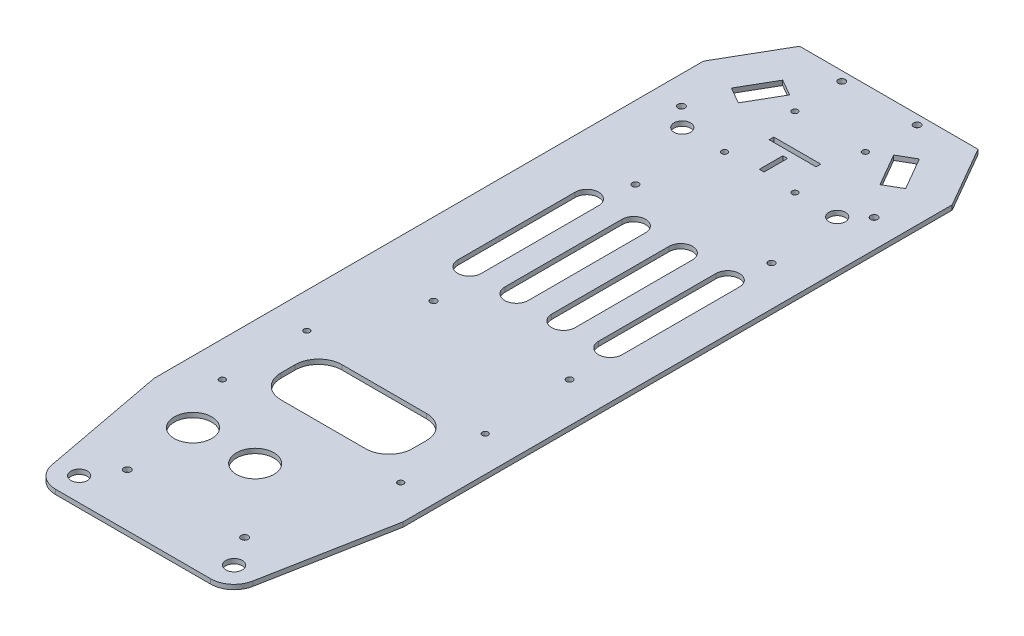
SolidWorks part; units mm, degrees
material "Epoxy, renforcé"
ref_plane "Plan de face" through (0, 0, 0) normal (0, 0, 1) x (1, 0, 0)
ref_plane "Plan de dessus" through (0, 0, 0) normal (0, 1, 0) x (1, 0, 0)
ref_plane "Plan de droite" through (0, 0, 0) normal (1, 0, 0) x (0, 0, -1)
sketch "Esquisse1" plane through (0, 0, 0) normal (0, 1, 0) x (1, 0, 0)
  line L0 (-33, 128.5) -> (33, 128.5) construction
  line L1 (33, 128.5) -> (33, -128.5) construction
  line L2 (33, -128.5) -> (-33, -128.5) construction
  line L3 (-33, -128.5) -> (-33, 128.5) construction
  line L4 (0, 128.5) -> (0, 0) construction
  line L5 (33, 0) -> (0, 0) construction
  line L6 (53, 183.5) -> (-53, 183.5)
  line L7 (-53, 183.5) -> (-53, -148.5)
  line L8 (-53, -148.5) -> (53, -148.5)
  line L9 (53, 183.5) -> (53, -148.5)
  circle A0 centre (-33, 128.5) radius 3.5
  circle A1 centre (-33, -128.5) radius 3.5
  circle A2 centre (33, 128.5) radius 3.5
  circle A3 centre (33, -128.5) radius 3.5
  point P17 (0, -148.5)
  point P18 (0, 183.5)
  dimension "D1" = 7
  dimension "D2" = 7
  dimension "D3" = 7
  dimension "D4" = 7
  dimension "D5" = 66
  dimension "D6" = 257
  dimension "D7" = 55
  dimension "D8" = 20
  dimension "D9" = 20
extrude "Boss.-Extru.1" add sketch "Esquisse1" along normal blind 2
sketch "Esquisse3" plane through (0, 2, 0) normal (0, 1, 0) x (1, 0, 0)
  line L0 (-22, 11.5) -> (-22, 97.5) construction
  line L1 (-22, 97.5) -> (36, 97.5) construction
  line L2 (36, 97.5) -> (36, 11.5) construction
  line L3 (36, 11.5) -> (-22, 11.5) construction
  line L4 (53, -148.5) -> (53, 183.5) construction
  line L5 (53, 183.5) -> (-53, 183.5) construction
  circle A4 centre (-22, 11.5) radius 1.375
  circle A5 centre (-22, 97.5) radius 1.375
  circle A6 centre (36, 97.5) radius 1.375
  circle A7 centre (36, 11.5) radius 1.375
  dimension "D1" = 86
  dimension "D2" = 58
  dimension "D3" = 17
  dimension "D4" = 86
extrude "Enlèv. mat.-Extru.1" cut sketch "Esquisse3" against normal through all
chamfer "Chanfrein1" distance 15 angle 60 2 edges at (-53, 1, -183.5) (53, 1, -183.5) first distance on face at (0, 1, -183.5)
sketch "Esquisse4" plane through (0, 2, 0) normal (0, 1, 0) x (1, 0, 0)
  line L0 (0, -62.5) -> (0, -148.5) construction
  line L1 (38, -62.5) -> (-38, -62.5) construction
  line L2 (38, -62.5) -> (38, -26.5) construction
  line L3 (38, -26.5) -> (-38, -26.5) construction
  line L4 (-38, -62.5) -> (-38, -26.5) construction
  line L5 (-53, -148.5) -> (53, -148.5) construction
  line L6 (38, 183.5) -> (-38, 183.5) construction
  line L7 (-28, -57.5) -> (28, -57.5)
  line L8 (-28, -57.5) -> (-28, -31.5)
  line L9 (-28, -31.5) -> (28, -31.5)
  line L10 (28, -57.5) -> (28, -31.5)
  circle A0 centre (38, -62.5) radius 1.25
  circle A1 centre (38, -26.5) radius 1.25
  circle A2 centre (-38, -62.5) radius 1.25
  circle A3 centre (-38, -26.5) radius 1.25
  dimension "D3" = 2.5
  dimension "D4" = 2.5
  dimension "D5" = 2.5
  dimension "D6" = 2.5
  dimension "D1" = 76
  dimension "D2" = 36
  dimension "D7" = 210
  dimension "D8" = 10
  dimension "D9" = 10
  dimension "D10" = 10
  dimension "D11" = 10
extrude "Enlèv. mat.-Extru.2" cut sketch "Esquisse4" against normal blind 10
fillet "Congé1" radius 10 4 edges at (28, 1, 57.5) (28, 1, 31.5) (-28, 1, 31.5) (-28, 1, 57.5)
sketch "Esquisse5" plane through (0, 2, 0) normal (0, 1, 0) x (1, 0, 0)
  line L1 (-22, 11.5) -> (36, 11.5) construction
  line L2 (-22, 11.5) -> (-22, 97.5) construction
  line L3 (-22, 97.5) -> (36, 97.5) construction
  line L4 (36, 11.5) -> (36, 97.5) construction
  line L5 (-17, 16.5) -> (23.5, 16.5)
  line L6 (-17, 16.5) -> (-17, 92.5)
  line L7 (-17, 92.5) -> (23.5, 92.5)
  line L8 (23.5, 16.5) -> (23.5, 92.5)
  dimension "D1" = 10
  dimension "D2" = 10
  dimension "D3" = 25
  dimension "D4" = 10
extrude "Enlèv. mat.-Extru.3" [suppressed] cut sketch "Esquisse5" against normal blind 10
fillet "Congé2" [suppressed] radius 10
sketch "Esquisse6" plane through (0, 2, 0) normal (0, 1, 0) x (1, 0, 0)
  line L0 (0, 183.5) -> (0, 143.5) construction
  line L2 (38, 183.5) -> (-38, 183.5) construction
  line L3 (15, 128.5) -> (-15, 128.5) construction
  line L4 (15, 128.5) -> (15, 158.5) construction
  line L5 (15, 158.5) -> (-15, 158.5) construction
  line L6 (-15, 128.5) -> (-15, 158.5) construction
  line L7 (15, 128.5) -> (-15, 158.5) construction
  line L8 (15, 158.5) -> (-15, 128.5) construction
  line L9 (-10, 142.5) -> (10, 142.5)
  line L10 (-10, 142.5) -> (-10, 144.5)
  line L11 (-10, 144.5) -> (10, 144.5)
  line L12 (10, 142.5) -> (10, 144.5)
  line L13 (-10, 142.5) -> (10, 144.5) construction
  line L14 (-10, 144.5) -> (10, 142.5) construction
  line L15 (-1.1799, 129.5) -> (0.8201, 129.5)
  line L16 (-1.1799, 129.5) -> (-1.1799, 139.5)
  line L17 (-1.1799, 139.5) -> (0.8201, 139.5)
  line L18 (0.8201, 129.5) -> (0.8201, 139.5)
  line L19 (-1.1799, 129.5) -> (0.8201, 139.5) construction
  line L20 (-1.1799, 139.5) -> (0.8201, 129.5) construction
  circle A0 centre (-15, 128.5) radius 1.25
  circle A1 centre (15, 128.5) radius 1.25
  circle A2 centre (-15, 158.5) radius 1.25
  circle A3 centre (15, 158.5) radius 1.25
  point P16 (-0.1799, 134.5)
  dimension "D4" = 2.5
  dimension "D5" = 2.5
  dimension "D6" = 2.5
  dimension "D7" = 2.5
  dimension "D1" = 30
  dimension "D2" = 30
  dimension "D3" = 40
  dimension "D8" = 20
  dimension "D9" = 2
  dimension "D10" = 10
  dimension "D11" = 2
  dimension "D12" = 3
extrude "Enlèv. mat.-Extru.4" cut sketch "Esquisse6" against normal blind 10
sketch "Esquisse7" plane through (0, 2, 0) normal (0, 1, 0) x (1, 0, 0)
  line L0 (0, -86.5) -> (0, -148.5) construction
  line L1 (-53, -148.5) -> (53, -148.5) construction
  line L2 (0, -86.5) -> (-53, -86.5) construction
  line L3 (-53, 157.5192) -> (-53, -148.5) construction
  line L4 (38, 183.5) -> (-38, 183.5) construction
  circle A0 centre (0, -86.5) radius 8
  circle A1 centre (-26.5, -86.5) radius 8
  dimension "D1" = 16
  dimension "D3" = 16
  dimension "D2" = 270
extrude "Enlèv. mat.-Extru.5" cut sketch "Esquisse7" against normal blind 10
sketch "Esquisse8" plane through (0, 2, 0) normal (0, 1, 0) x (1, 0, 0)
  line L0 (38, 183.5) -> (-38, 183.5)
  line L1 (38, 183.5) -> (-38, 183.5) construction
  line L2 (-38, 183.5) -> (-53, 157.5192)
  line L3 (-53, 157.5192) -> (-53, -76.5)
  line L4 (-53, 157.5192) -> (-53, -148.5) construction
  line L5 (-53, -76.5) -> (-42.8262, -130.3562)
  line L6 (-33, -138.5) -> (33, -138.5)
  line L7 (0, -148.5) -> (0, 183.5) construction
  line L8 (-53, -148.5) -> (53, -148.5) construction
  line L9 (53, -76.5) -> (42.8262, -130.3562)
  line L10 (53, 157.5192) -> (53, -76.5)
  line L11 (38, 183.5) -> (53, 157.5192)
  arc A0 (-42.8262, -130.3562) -> (-33, -138.5) centre (-33, -128.5) ccw
  arc A1 (42.8262, -130.3562) -> (33, -138.5) centre (33, -128.5) cw
  point P22 (0, -138.5)
  dimension "D1" = 20
  dimension "D2" = 260
extrude "Enlèv. mat.-Extru.6" cut sketch "Esquisse8" against normal blind 10 flip side to cut
sketch "Esquisse9" plane through (0, 2, 0) normal (0, 1, 0) x (1, 0, 0)
  line L0 (53, 10.4239) -> (-53, 10.4239) construction
  line L1 (53, -76.5) -> (53, 157.5192) construction
  line L2 (-53, 157.5192) -> (-53, -76.5) construction
  circle A0 centre (45, 10.4239) radius 3.5
  circle A1 centre (-45, 10.4239) radius 3.5
  dimension "D1" = 7
  dimension "D3" = 7
  dimension "D2" = 8
  dimension "D4" = 8
extrude "Enlèv. mat.-Extru.7" [suppressed] cut sketch "Esquisse9" against normal blind 10
sketch "Esquisse10" plane through (0, 0, 0) normal (0, -1, 0) x (1, 0, 0)
  line L0 (38, -183.5) -> (53, -157.5192) construction
  line L1 (55.5, -153.1891) -> (37.3135, -142.6891) construction
  line L2 (55.5, -153.1891) -> (38, -183.5) construction
  line L3 (38, -183.5) -> (19.8135, -173) construction
  line L4 (37.3135, -142.6891) -> (19.8135, -173) construction
  line L5 (55.5, -153.1891) -> (19.8135, -173) construction
  line L6 (38, -183.5) -> (37.3135, -142.6891) construction
  line L7 (28.5635, -157.8446) -> (37.6567, -163.0946) construction
  line L8 (32.5635, -150.9164) -> (30.1819, -149.5414)
  line L9 (30.1819, -149.5414) -> (26.1868, -156.461)
  line L10 (32.5635, -150.9164) -> (37.1101, -153.5414)
  line L11 (37.1101, -153.5414) -> (29.1101, -167.3978)
  line L12 (24.5635, -164.7728) -> (29.1101, -167.3978)
  line L13 (22.1819, -163.3978) -> (26.1868, -156.461)
  line L14 (24.5635, -164.7728) -> (22.1819, -163.3978)
  line L15 (0, -183.5) -> (0, -146.2698) construction
  line L16 (28.5635, -157.8446) -> (16.0635, -179.4952) construction
  line L18 (38, -183.5) -> (-38, -183.5) construction
  line L19 (-28.5635, -157.8446) -> (-37.6567, -163.0946) construction
  line L20 (-38, -183.5) -> (-37.3135, -142.6891) construction
  line L21 (-55.5, -153.1891) -> (-19.8135, -173) construction
  line L22 (-37.3135, -142.6891) -> (-19.8135, -173) construction
  line L23 (-38, -183.5) -> (-19.8135, -173) construction
  line L24 (-55.5, -153.1891) -> (-38, -183.5) construction
  line L25 (-55.5, -153.1891) -> (-37.3135, -142.6891) construction
  line L26 (-24.5635, -164.7728) -> (-22.1819, -163.3978)
  line L27 (-22.1819, -163.3978) -> (-26.1868, -156.461)
  line L28 (-24.5635, -164.7728) -> (-29.1101, -167.3978)
  line L29 (-37.1101, -153.5414) -> (-29.1101, -167.3978)
  line L30 (-32.5635, -150.9164) -> (-37.1101, -153.5414)
  line L31 (-30.1819, -149.5414) -> (-26.1868, -156.461)
  line L32 (-32.5635, -150.9164) -> (-30.1819, -149.5414)
  circle A0 centre (16.0635, -179.4952) radius 1.5
  circle A1 centre (41.0635, -136.1939) radius 1.5
  circle A2 centre (-41.0635, -136.1939) radius 1.5
  circle A3 centre (-16.0635, -179.4952) radius 1.5
  point P0 (37.6567, -163.0946)
  point P16 (33.1101, -160.4696)
  point P38 (-33.1101, -160.4696)
  dimension "D3" = 8
  dimension "D5" = 3
  dimension "D1" = 21
  dimension "D2" = 35
  dimension "D4" = 8
  dimension "D6" = 25
extrude "Enlèv. mat.-Extru.8" cut sketch "Esquisse10" against normal blind 10
sketch "Esquisse11" plane through (0, 0, 0) normal (0, -1, 0) x (1, 0, 0)
  line L0 (25, 116) -> (0, 116) construction
  line L1 (17.5, 126.5) -> (-17.5, 126.5) construction
  line L2 (17.5, 126.5) -> (17.5, 105.5) construction
  line L3 (17.5, 105.5) -> (-17.5, 105.5) construction
  line L4 (-17.5, 126.5) -> (-17.5, 105.5) construction
  line L5 (17.5, 126.5) -> (-17.5, 105.5) construction
  line L6 (17.5, 105.5) -> (-17.5, 126.5) construction
  line L7 (0, 116) -> (0, 105.5) construction
  line L8 (0, 138.5) -> (0, 126.5) construction
  line L9 (-33, 138.5) -> (33, 138.5) construction
  circle A0 centre (25, 116) radius 1.5
  circle A1 centre (-25, 116) radius 1.5
  point P0 (0, 116)
  dimension "D3" = 3
  dimension "D1" = 21
  dimension "D2" = 35
  dimension "D4" = 25
  dimension "D5" = 12
extrude "Enlèv. mat.-Extru.9" cut sketch "Esquisse11" against normal blind 10
sketch "Esquisse12" plane through (0, 0, 0) normal (0, -1, 0) x (1, 0, 0)
  line L0 (33, -31.8433) -> (33, -81.8433) construction
  line L1 (38, -31.8433) -> (38, -81.8433)
  line L2 (28, -31.8433) -> (28, -81.8433)
  line L3 (13, -31.8433) -> (13, -81.8433) construction
  line L4 (18, -31.8433) -> (18, -81.8433)
  line L5 (8, -31.8433) -> (8, -81.8433)
  line L6 (-7, -31.8433) -> (-7, -81.8433) construction
  line L7 (-2, -31.8433) -> (-2, -81.8433)
  line L8 (-12, -31.8433) -> (-12, -81.8433)
  line L9 (-27, -31.8433) -> (-27, -81.8433) construction
  line L10 (-22, -31.8433) -> (-22, -81.8433)
  line L11 (-32, -31.8433) -> (-32, -81.8433)
  line L12 (53, 76.5) -> (53, -157.5192) construction
  arc A0 (38, -31.8433) -> (28, -31.8433) centre (33, -31.8433) ccw
  arc A1 (28, -81.8433) -> (38, -81.8433) centre (33, -81.8433) ccw
  arc A2 (18, -31.8433) -> (8, -31.8433) centre (13, -31.8433) ccw
  arc A3 (8, -81.8433) -> (18, -81.8433) centre (13, -81.8433) ccw
  arc A4 (-2, -31.8433) -> (-12, -31.8433) centre (-7, -31.8433) ccw
  arc A5 (-12, -81.8433) -> (-2, -81.8433) centre (-7, -81.8433) ccw
  arc A6 (-22, -31.8433) -> (-32, -31.8433) centre (-27, -31.8433) ccw
  arc A7 (-32, -81.8433) -> (-22, -81.8433) centre (-27, -81.8433) ccw
  point P2 (33, -56.8433)
  point P10 (13, -56.8433)
  point P17 (-7, -56.8433)
  point P24 (-27, -56.8433)
  dimension "D1" = 10
  dimension "D2" = 50
  dimension "D4" = 20
  dimension "D3" = 4
extrude "Enlèv. mat.-Extru.10" cut sketch "Esquisse12" against normal blind 10
